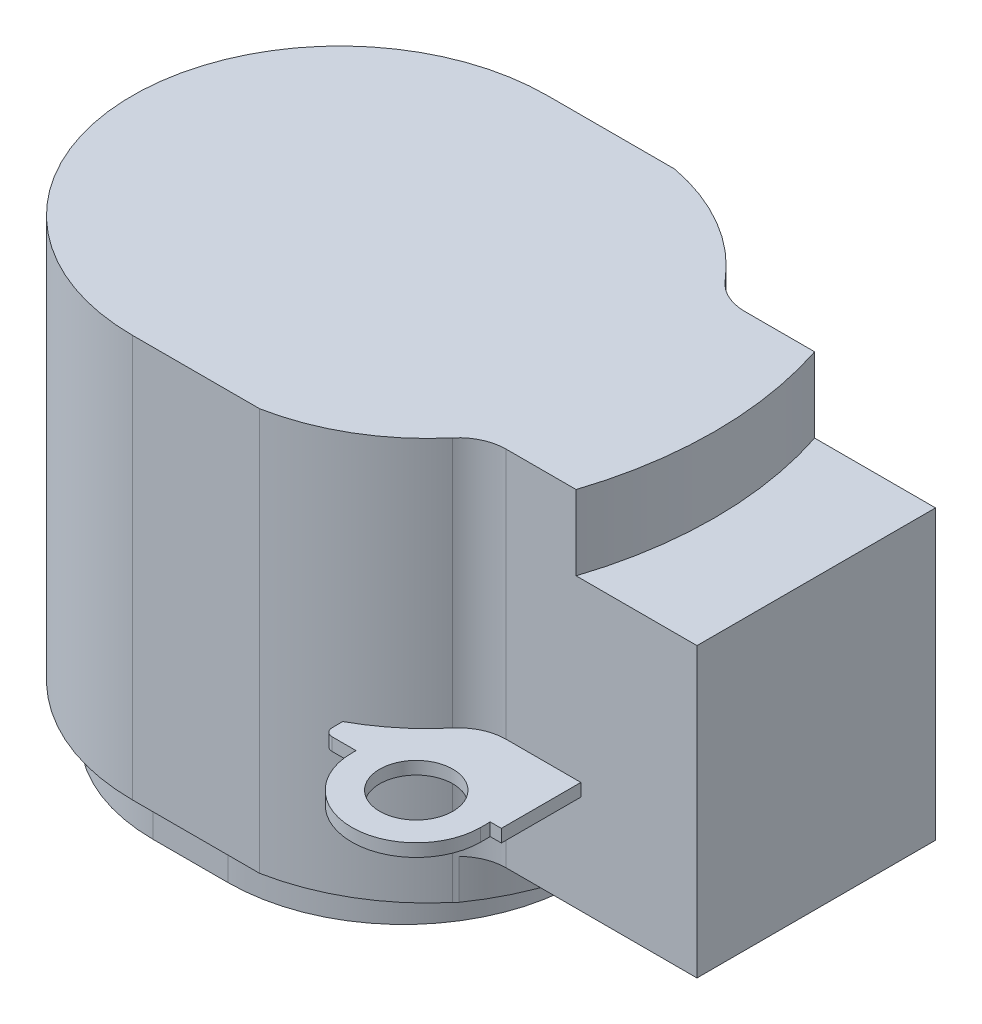
SolidWorks part; units mm, degrees
ref_plane "Front Plane" through (0, 0, 0) normal (0, 0, 1) x (1, 0, 0)
ref_plane "Top Plane" through (0, 0, 0) normal (0, 1, 0) x (1, 0, 0)
ref_plane "Right Plane" through (0, 0, 0) normal (1, 0, 0) x (0, 0, -1)
sketch "Sketch1" plane through (0, 0, 0) normal (0, 1, 0) x (1, 0, 0)
  line L5 (-4, 0) -> (1.4987, 0) construction
  line L6 (-4, 13.05) -> (4, 13.05)
  line L14 (-4, -13.05) -> (4, -13.05)
  line L16 (25.95, 7.5) -> (13.95, 7.5)
  line L17 (25.95, 7.5) -> (25.95, -7.5)
  line L18 (25.95, -7.5) -> (13.95, -7.5)
  arc A7 (-4, 13.05) -> (-4, -13.05) centre (-4, 0) ccw
  arc A8 (4, -13.05) -> (11.6566, -8.566) centre (1.4987, 0) ccw
  arc A9 (11.6566, 8.566) -> (4, 13.05) centre (1.4987, 0) ccw
  arc A10 (13.95, -7.5) -> (11.6566, -8.566) centre (13.95, -10.5) ccw
  arc A11 (13.95, 7.5) -> (11.6566, 8.566) centre (13.95, 10.5) cw
  point P2 (0, 0)
  point P11 (25.95, 0)
  point P12 (0, 0)
  point P17 (12.4673, 7.5)
  point P18 (-17.05, 0)
  dimension "D1" = 26.1
  dimension "D5" = 3
  dimension "D4" = 12
  dimension "D2" = 8
  dimension "D3" = 15
  dimension "D6" = 43
extrude "Boss-Extrude1" add sketch "Sketch1" against normal blind 28.8
sketch "Sketch2" plane through (0, 0, 0) normal (0, 1, 0) x (1, 0, 0)
  line L0 (0, 0) -> (-4.7, 0) construction
  line L1 (0, -9.05) -> (-4.7, -9.05)
  line L2 (0, 9.05) -> (-4.7, 9.05)
  arc A1 (0, -9.05) -> (0, 9.05) centre (0, 0) ccw
  arc A2 (-4.7, 9.05) -> (-4.7, -9.05) centre (-4.7, 0) ccw
  arc A4 (-4, 13.05) -> (-4, -13.05) centre (-4, 0) ccw construction
  point P2 (0, 0)
  point P3 (-2.35, 0)
  point P9 (-13.75, 0)
  point P11 (0, 0)
  point P12 (0, 0)
  point P14 (0, 0)
  point P17 (-17.05, 0)
  point P18 (0, 0)
  dimension "D1" = 3.3
  dimension "D2" = 18.1
extrude "Cut-Extrude1" cut sketch "Sketch2" against normal through all
sketch "Sketch7" plane through (0, 0, 0) normal (0, 1, 0) x (1, 0, 0)
  line L0 (-4.7, 0) -> (0, 0) construction
  line L1 (-4.7, 10.05) -> (0, 10.05)
  line L2 (-4.7, -10.05) -> (0, -10.05)
  line L3 (0, 9.05) -> (-4.7, 9.05) construction
  arc A0 (-4.7, 10.05) -> (-4.7, -10.05) centre (-4.7, 0) ccw
  arc A1 (0, -10.05) -> (0, 10.05) centre (0, 0) ccw
  point P4 (-2.35, 0)
  dimension "D1" = 1
extrude "Boss-Extrude3" add sketch "Sketch7" against normal blind 1
sketch "Sketch3" plane through (0, 0, 0) normal (0, 1, 0) x (1, 0, 0)
  line L1 (25.95, 7.5) -> (18.35, 7.5)
  line L2 (25.95, 7.5) -> (25.95, -7.5)
  line L3 (25.95, -7.5) -> (18.35, -7.5)
  line L6 (25.95, -7.5) -> (25.95, 7.5) construction
  arc A0 (18.35, 7.5) -> (18.35, -7.5) centre (-4.4875, 0) cw
  point P8 (19.55, 0)
  point P9 (0, 0)
  point P11 (0, 0)
  dimension "D2" = 1.2
  dimension "D1" = 7.6
extrude "Cut-Extrude2" cut sketch "Sketch3" against normal blind 4.7
ref_plane "Plane1" through (0, -15.8, 0) normal (0, 1, 0) x (1, 0, 0)
sketch "Sketch4" plane through (0, -15.8, 0) normal (0, 1, 0) x (1, 0, 0)
  line L0 (13.9, 13.1) -> (13.9, -13.1) construction
  line L1 (17.95, 13.1) -> (17.95, -13.1)
  line L2 (9.85, 13.1) -> (9.85, -13.1)
  line L4 (13.9, 0) -> (-21.7278, 0) construction
  line L5 (9.85, 12.8351) -> (8.35, 12.8351)
  line L6 (9.85, 12.8351) -> (9.85, 10.1067)
  line L7 (9.85, 10.1067) -> (7.85, 10.1067)
  line L8 (7.85, 12.3351) -> (7.85, 10.1067)
  line L10 (17.95, 12.5) -> (18.65, 12.5)
  line L11 (17.95, 12.5) -> (17.95, 6.669)
  line L12 (17.95, 6.669) -> (18.65, 6.669)
  line L13 (18.65, 12.5) -> (18.65, 6.669)
  line L22 (18.65, -12.5) -> (18.65, -6.669)
  line L23 (17.95, -6.669) -> (18.65, -6.669)
  line L24 (17.95, -12.5) -> (17.95, -6.669)
  line L25 (17.95, -12.5) -> (18.65, -12.5)
  line L26 (7.85, -12.3351) -> (7.85, -10.1067)
  line L27 (9.85, -10.1067) -> (7.85, -10.1067)
  line L28 (9.85, -12.8351) -> (9.85, -10.1067)
  line L29 (9.85, -12.8351) -> (8.35, -12.8351)
  line L30 (25.95, -7.5) -> (25.95, 7.5) construction
  line L31 (25.95, 7.5) -> (18.35, 7.5) construction
  arc A0 (17.95, 13.1) -> (9.85, 13.1) centre (13.9, 13.1) ccw
  arc A1 (9.85, -13.1) -> (17.95, -13.1) centre (13.9, -13.1) ccw
  circle A2 centre (13.9, 13.1) radius 2.3
  circle A3 centre (13.9, -13.1) radius 2.3
  arc A5 (8.35, 12.8351) -> (7.85, 12.3351) centre (8.35, 12.3351) ccw
  arc A6 (8.35, -12.8351) -> (7.85, -12.3351) centre (8.35, -12.3351) cw
  arc A8 (11.6566, 8.566) -> (4, 13.05) centre (1.4987, 0) ccw construction
  point P2 (13.9, 0)
  point P9 (13.9, 17.15)
  point P10 (13.9, -17.15)
  point P21 (0, 0)
  point P23 (9.85, 10.3351)
  point P43 (7.85, 12.8351)
  point P45 (7.85, -12.8351)
  point P46 (9.85, -10.3351)
  point P47 (0, 0)
  point P51 (0, 0)
  dimension "D2" = 4.05
  dimension "D4" = 4.6
  dimension "D5" = 4.6
  dimension "D6" = 2.5
  dimension "D10" = 0.5
  dimension "D3" = 34.3
  dimension "D7" = 2
  dimension "D8" = 8
  dimension "D9" = 0.7
  dimension "D11" = 5
extrude "Boss-Extrude2" add sketch "Sketch4" against normal blind 0.8 contours L26 A1 L1 A0 L6 L2 A3 A2 | L5 L8 L7 L2 L6 | L13 L10 L1 L12 | L1 L25 L22 L23 | L26 L2 A6 region at (13.9, -15.8, 0) region at (18.3, -15.8, -9.5845) region at (8.8588, -15.8, -11.4585) region at (18.3, -15.8, 9.5845) region at (8.8588, -15.8, 11.4585)
sketch "Sketch5" plane through (0, -28.8, 0) normal (0, -1, 0) x (1, 0, 0)
  line L0 (-4.7, 0) -> (0, 0) construction
  line L1 (-4.7, 11.05) -> (0, 11.05)
  line L2 (-4.7, -11.05) -> (0, -11.05)
  line L3 (-4.7, 9.05) -> (0, 9.05) construction
  arc A0 (-4.7, 11.05) -> (-4.7, -11.05) centre (-4.7, 0) ccw
  arc A1 (0, -11.05) -> (0, 11.05) centre (0, 0) ccw
  point P4 (-2.35, 0)
  arc M5 (0, 9.05) -> (0, -9.05) centre (0, 0) cw
  line M6 (0, -9.05) -> (-4.7, -9.05)
  arc M7 (-4.7, -9.05) -> (-4.7, 9.05) centre (-4.7, 0) cw
  line M8 (-4.7, 9.05) -> (0, 9.05)
  dimension "D1" = 2
extrude "Cut-Extrude3" cut sketch "Sketch5" against normal blind 3.5 flip side to cut contours L2 A1 L1 A0 M8 M5 M6 M7 region at (-2.35, -28.8, 10.7026)
sketch "Sketch6" plane through (0, -25.3, 0) normal (0, -1, 0) x (1, 0, 0)
  line L0 (7.85, 12.3351) -> (7.85, 11.6713) construction
  line L2 (-0.9152, 14.4718) -> (-20.7495, 14.4718)
  line L4 (0, -14.5007) -> (-20.7495, -14.5007)
  line L5 (-20.7495, 14.4718) -> (-20.7495, -14.5007)
  arc A0 (0, -14.5007) -> (-0.9152, 14.4718) centre (0, 0) ccw
  arc A2 (11.6566, 8.566) -> (13.95, 7.5) centre (13.95, 10.5) ccw construction
  point P1 (0, 0)
  point P3 (11.85, 8.3576)
  point P5 (0, 0)
  point P15 (1.35, -13.4201)
  dimension "D1" = 4
extrude "Cut-Extrude4" cut sketch "Sketch6" against normal blind 2.5 flip side to cut
